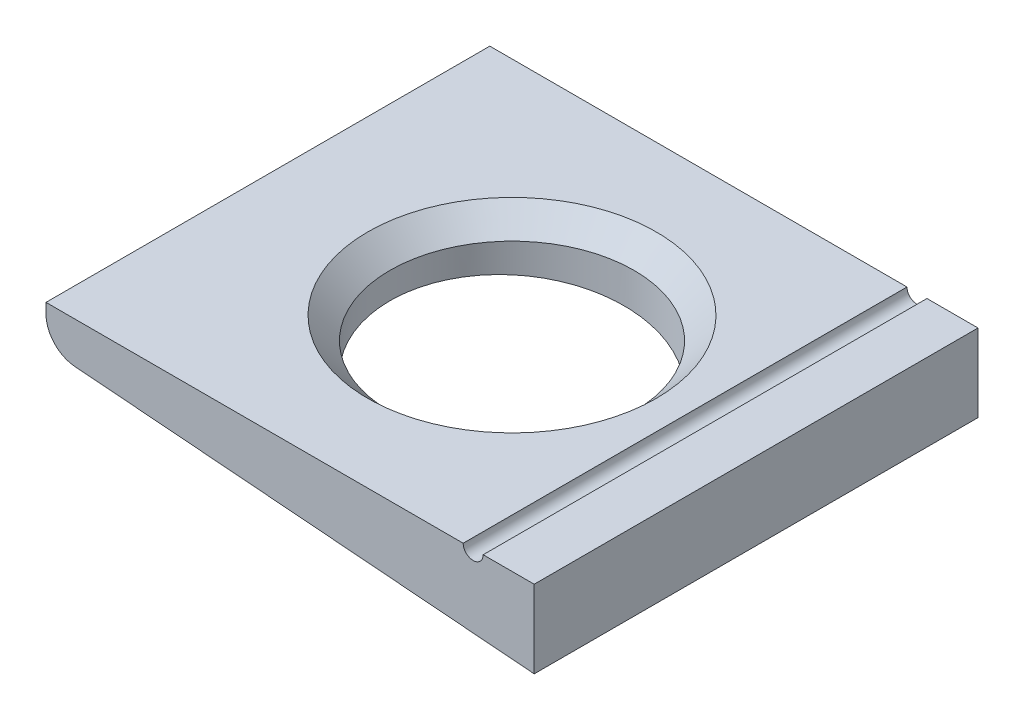
SolidWorks part; units mm, degrees
extrude "Base-Extrude" add sketch "Sketch1" along normal mid plane 40
sketch "Sketch1" plane through (0, 0, 0) normal (0, 0, 1) x (1, 0, 0)
  line L0 (22, 0) -> (-22, 0)
  line L1 (22, 0) -> (22, -7)
  line L2 (-22, 0) -> (-22, -0.9139)
  line L3 (22, -7) -> (-19.422, -3.7051)
  line L4 (0, 0) -> (0, -5.25) construction
  arc A0 (-19.422, -3.7051) -> (-22, -0.9139) centre (-19.2, -0.9139) cw
  dimension "D2" = 22
ref_plane "Plane1" through (0, 0, 0) normal (0, 0, 1) x (1, 0, 0)
ref_plane "Plane2" through (0, 0, 0) normal (0, 1, 0) x (1, 0, 0)
ref_plane "Plane3" through (0, 0, 0) normal (1, 0, 0) x (0, 0, -1)
sketch "Sketch2" plane through (0, 0, 0) normal (0, 1, 0) x (-1, 0, 0)
  circle A0 centre (0, 0) radius 11
extrude "Cut-Extrude1" cut sketch "Sketch2" against normal through all
sketch "Sketch3" plane through (0, 0, 20) normal (0, 0, 1) x (1, 0, 0)
  line L0 (22, 0) -> (-22, 0) construction
  circle A0 centre (16.5, 0) radius 0.9
  dimension "T" = 0.9
  dimension "D2" = 16.5
extrude "ID-Grooves" cut sketch "Sketch3" against normal through all
chamfer "Chamfer1" distance 2 angle 45 1 edges at (-11, 0, 0)
equation "\"D2@Sketch1\" = \"B@Sketch1\" / 2"
equation "\"D2@Sketch3\" =  ( \"D@Sketch2\" / 2 )  +  ( \"B@Sketch1\" -  \"D@Sketch2\" )  / 4"
